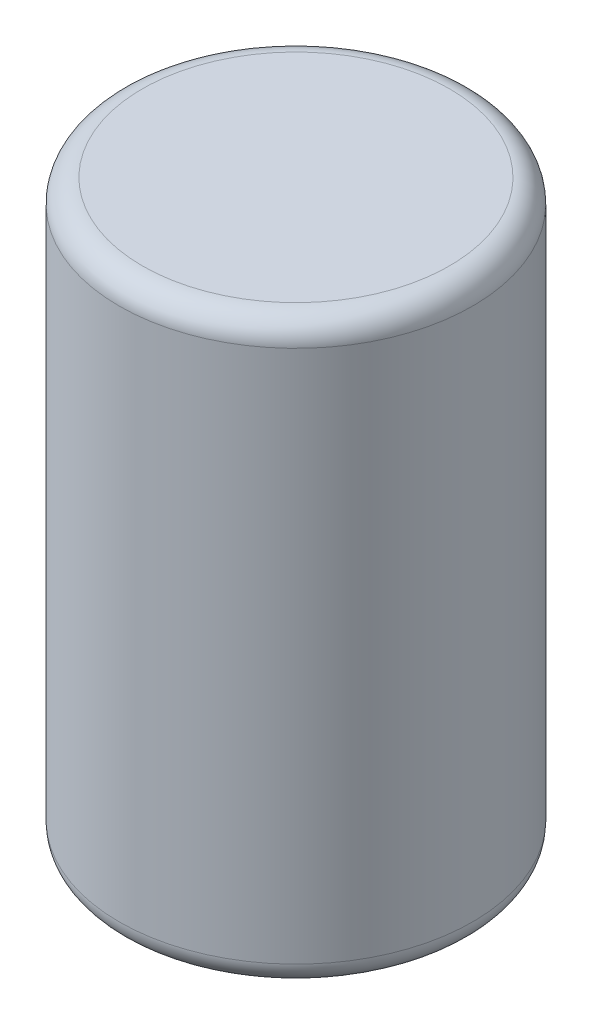
SolidWorks part; units mm, degrees
ref_plane "Front Plane" through (0, 0, 0) normal (0, 0, 1) x (1, 0, 0)
ref_plane "Top Plane" through (0, 0, 0) normal (0, 1, 0) x (1, 0, 0)
ref_plane "Right Plane" through (0, 0, 0) normal (1, 0, 0) x (0, 0, -1)
sketch "Sketch2" plane through (0, 0, 0) normal (0, 1, 0) x (1, 0, 0)
  circle A0 centre (0, 0) radius 76.2
  dimension "D1" = 152.4
extrude "Boss-Extrude1" add sketch "Sketch2" along normal blind 250
fillet "Fillet1" radius 10 2 edges at (0, 0, 76.2) (0, 250, 76.2)
